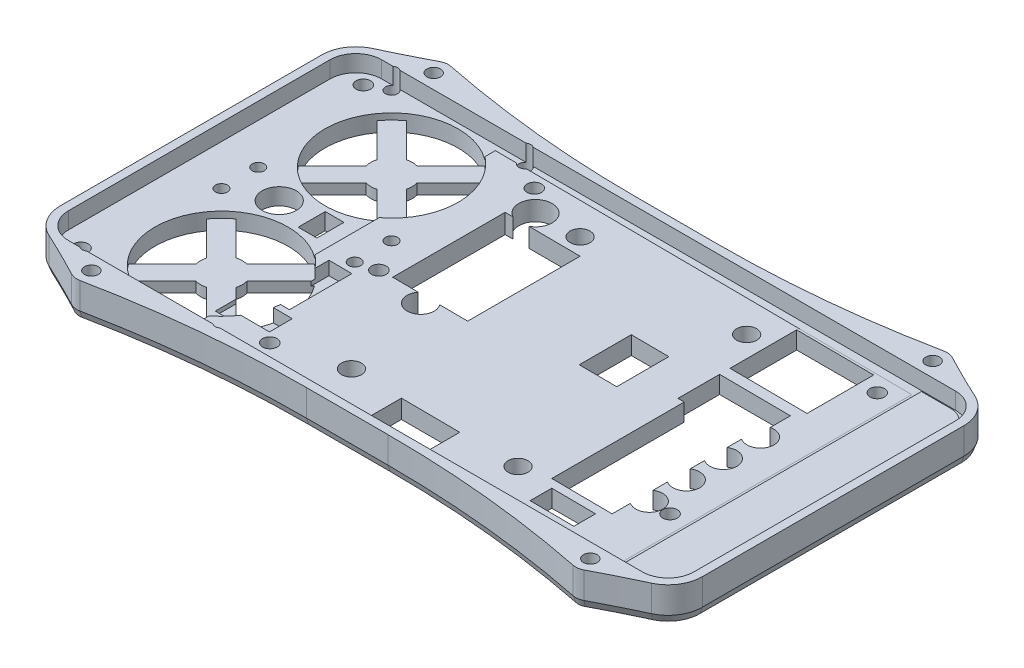
SolidWorks part; units mm, degrees
ref_plane "前视基准面" through (0, 0, 0) normal (0, 0, 1) x (1, 0, 0)
ref_plane "上视基准面" through (0, 0, 0) normal (0, 1, 0) x (1, 0, 0)
ref_plane "右视基准面" through (0, 0, 0) normal (1, 0, 0) x (0, 0, -1)
sketch "草图1" plane through (0, 0, 0) normal (0, 1, 0) x (1, 0, 0)
  line L0 (6, 0.2) -> (143.8, 0.2)
  line L1 (6, 0) -> (143.8, 0) construction
  line L2 (0, -6) -> (0, -68.8) construction
  line L3 (6, -74.8) -> (143.8, -74.8) construction
  line L4 (149.8, -6) -> (149.8, -68.8) construction
  line L5 (150, -6) -> (150, -68.8)
  line L6 (6, -75) -> (143.8, -75)
  line L7 (-0.2, -6) -> (-0.2, -68.8)
  arc A0 (143.8, 0) -> (149.8, -6) centre (143.8, -6) cw construction
  arc A1 (143.8, -74.8) -> (149.8, -68.8) centre (143.8, -68.8) ccw construction
  arc A2 (0, -68.8) -> (6, -74.8) centre (6, -68.8) ccw construction
  arc A3 (6, 0) -> (0, -6) centre (6, -6) ccw construction
  arc A4 (143.8, 0.2) -> (150, -6) centre (143.8, -6) cw
  arc A5 (143.8, -75) -> (150, -68.8) centre (143.8, -68.8) ccw
  arc A6 (-0.2, -68.8) -> (6, -75) centre (6, -68.8) ccw
  arc A7 (6, 0.2) -> (-0.2, -6) centre (6, -6) ccw
  point P7 (149.8, 0)
  point P12 (0, -74.8)
  point P15 (0, 0)
  dimension "D3" = 6
  dimension "D1" = 74.8
  dimension "D2" = 149.8
  dimension "D4" = 0.2
extrude "凸台-拉伸1" add sketch "草图1" along normal blind 4
sketch "草图2" plane through (0, 0, 0) normal (0, -1, 0) x (-1, 0, 0)
  line L0 (-122.6, -55.35) -> (-108.9, -55.35)
  line L1 (-122.6, -69.85) -> (-108.9, -69.85)
  line L2 (-122.6, -69.85) -> (-122.6, -63.95)
  line L3 (-122.6, -63.95) -> (-108.9, -63.95)
  line L4 (-108.9, -69.85) -> (-108.9, -63.95)
  line L5 (-135.3, -1.25) -> (-35.3, -1.25) construction
  line L6 (-135.3, -1.25) -> (-135.3, -73.55) construction
  line L7 (-135.3, -73.55) -> (-35.3, -73.55) construction
  line L8 (-35.3, -1.25) -> (-35.3, -73.55) construction
  line L9 (-108.9, -61.25) -> (-108.9, -55.35)
  line L10 (-122.6, -61.25) -> (-108.9, -61.25)
  line L11 (-122.6, -61.25) -> (-122.6, -55.35)
  line L12 (-122.6, -46.75) -> (-108.9, -46.75)
  line L13 (-108.9, -52.65) -> (-108.9, -46.75)
  line L14 (-122.6, -52.65) -> (-108.9, -52.65)
  line L15 (-122.6, -52.65) -> (-122.6, -46.75)
  line L16 (-122.6, -38.15) -> (-108.9, -38.15)
  line L17 (-108.9, -44.05) -> (-108.9, -38.15)
  line L18 (-122.6, -44.05) -> (-108.9, -44.05)
  line L19 (-122.6, -44.05) -> (-122.6, -38.15)
  line L20 (0, -6) -> (0, -68.8) construction
  line L21 (-35.3, -73.55) -> (-0.8, -73.55) construction
  line L22 (-120.25, -26.65) -> (-111.25, -26.65) construction
  line L23 (-120.25, -26.65) -> (-120.25, -33.15) construction
  line L24 (-120.25, -33.15) -> (-111.25, -33.15) construction
  line L25 (-111.25, -26.65) -> (-111.25, -33.15) construction
  line L26 (-85.8, -48.75) -> (-81.1, -48.75) construction
  line L27 (-85.8, -48.75) -> (-85.8, -58.15) construction
  line L28 (-85.8, -58.15) -> (-81.1, -58.15) construction
  line L29 (-81.1, -48.75) -> (-81.1, -58.15) construction
  line L30 (-71.5, -48.65) -> (-68.2, -48.65) construction
  line L31 (-71.5, -48.65) -> (-71.5, -57.55) construction
  line L32 (-71.5, -57.55) -> (-68.2, -57.55) construction
  line L33 (-68.2, -48.65) -> (-68.2, -57.55) construction
  line L34 (-43.1, -45.05) -> (-38.6, -45.05) construction
  line L35 (-43.1, -45.05) -> (-43.1, -59.05) construction
  line L36 (-43.1, -59.05) -> (-38.6, -59.05) construction
  line L37 (-38.6, -45.05) -> (-38.6, -59.05) construction
  line L38 (-45.3, -61.55) -> (-33.3, -61.55) construction
  line L39 (-45.3, -61.55) -> (-45.3, -66.05) construction
  line L40 (-45.3, -66.05) -> (-33.3, -66.05) construction
  line L41 (-33.3, -61.55) -> (-33.3, -66.05) construction
  line L42 (-0.8, -73.55) -> (-0.8, -1.25) construction
  line L43 (-0.8, -1.25) -> (-35.3, -1.25) construction
  line L44 (-149.8, -6) -> (-149.8, -68.8) construction
  line L45 (-30.8, -34.65) -> (-27.3, -34.65) construction
  line L46 (-30.8, -34.65) -> (-30.8, -40.15) construction
  line L47 (-30.8, -40.15) -> (-27.3, -40.15) construction
  line L48 (-27.3, -34.65) -> (-27.3, -40.15) construction
  line L49 (-120.75, -33.65) -> (-110.75, -33.65)
  line L50 (-110.75, -26.15) -> (-110.75, -33.65)
  line L51 (-120.75, -26.15) -> (-110.75, -26.15)
  line L52 (-120.75, -26.15) -> (-120.75, -33.65)
  line L53 (-86.3, -48.25) -> (-86.3, -58.65)
  line L54 (-86.3, -58.65) -> (-80.6, -58.65)
  line L55 (-80.6, -48.25) -> (-80.6, -58.65)
  line L56 (-86.3, -48.25) -> (-80.6, -48.25)
  line L57 (-72, -48.15) -> (-72, -58.05)
  line L58 (-72, -58.05) -> (-67.7, -58.05)
  line L59 (-67.7, -48.15) -> (-67.7, -58.05)
  line L60 (-72, -48.15) -> (-67.7, -48.15)
  line L61 (-31.3, -34.15) -> (-31.3, -40.65)
  line L62 (-31.3, -40.65) -> (-26.8, -40.65)
  line L63 (-26.8, -34.15) -> (-26.8, -40.65)
  line L64 (-31.3, -34.15) -> (-26.8, -34.15)
  line L65 (-43.6, -44.55) -> (-43.6, -59.55)
  line L66 (-43.6, -59.55) -> (-38.1, -59.55)
  line L67 (-38.1, -44.55) -> (-38.1, -59.55)
  line L68 (-43.6, -44.55) -> (-38.1, -44.55)
  line L69 (-45.8, -61.05) -> (-45.8, -66.55)
  line L70 (-45.8, -66.55) -> (-32.8, -66.55)
  line L71 (-32.8, -61.05) -> (-32.8, -66.55)
  line L72 (-45.8, -61.05) -> (-32.8, -61.05)
  circle A0 centre (-103.2, -9.35) radius 2 construction
  circle A1 centre (-103.2, -64.25) radius 2 construction
  circle A2 centre (-63.2, -64.25) radius 2 construction
  circle A3 centre (-63.2, -9.35) radius 2 construction
  circle A4 centre (-130.8, -5.6) radius 1.25 construction
  circle A5 centre (-131.1, -55.65) radius 1.25 construction
  circle A6 centre (-47.7, -4.85) radius 1.25 construction
  circle A7 centre (-48.1, -68.75) radius 1.25 construction
  circle A8 centre (-22.8, -70.3) radius 1.25 construction
  circle A9 centre (-5.05, -71.05) radius 1.25 construction
  circle A10 centre (-5.05, -3.25) radius 1.25 construction
  circle A11 centre (-19, -37.4) radius 3.6 construction
  circle A12 centre (-103.2, -9.35) radius 2.4
  circle A13 centre (-63.2, -9.35) radius 2.4
  circle A14 centre (-63.2, -64.25) radius 2.4
  circle A15 centre (-103.2, -64.25) radius 2.4
  circle A16 centre (-19, -37.4) radius 4.1
  circle A17 centre (-130.8, -5.6) radius 1.75
  circle A18 centre (-131.1, -55.65) radius 1.75
  circle A19 centre (-48.1, -68.75) radius 1.75
  circle A20 centre (-22.8, -70.3) radius 1.75
  circle A21 centre (-5.05, -71.05) radius 1.75
  circle A22 centre (-5.05, -3.25) radius 1.75
  circle A23 centre (-47.7, -4.85) radius 1.75
  circle A24 centre (-46.11, -40.57) radius 1.25 construction
  circle A25 centre (-46.11, -40.57) radius 1.75
  point P22 (0, -37.4)
  point P23 (-135.3, -37.4)
  point P28 (-115.75, -33.15)
  point P29 (-115.75, -38.15)
  point P30 (-111.25, -29.9)
  point P31 (-108.9, -41.1)
  point P79 (-0.8, -37.4)
  point P81 (-27.3, -37.4)
  dimension "D21" = 4
  dimension "D34" = 2.5
  dimension "D53" = 7.2
  dimension "D1" = 13.7
  dimension "D2" = 5.9
  dimension "D3" = 72.3
  dimension "D4" = 3.7
  dimension "D5" = 12.7
  dimension "D7" = 14.5
  dimension "D8" = 100
  dimension "D9" = 2.7
  dimension "D10" = 9
  dimension "D11" = 6.5
  dimension "D12" = 11.2
  dimension "D13" = 15.4
  dimension "D14" = 9.4
  dimension "D15" = 4.7
  dimension "D16" = 23.1
  dimension "D17" = 3.3
  dimension "D18" = 8.9
  dimension "D19" = 16
  dimension "D20" = 37.4
  dimension "D22" = 8.1
  dimension "D23" = 32.1
  dimension "D24" = 40
  dimension "D25" = 9.3
  dimension "D26" = 14
  dimension "D27" = 4.5
  dimension "D28" = 12
  dimension "D29" = 4.5
  dimension "D30" = 3.3
  dimension "D31" = 2
  dimension "D32" = 7.5
  dimension "D33" = 14.5
  dimension "D35" = 34.5
  dimension "D36" = 2
  dimension "D37" = 4.25
  dimension "D38" = 2.5
  dimension "D39" = 3.25
  dimension "D40" = 22
  dimension "D41" = 4.8
  dimension "D42" = 12.8
  dimension "D43" = 3.6
  dimension "D44" = 12.4
  dimension "D45" = 4.35
  dimension "D46" = 4.5
  dimension "D47" = 4.2
  dimension "D48" = 17.9
  dimension "D49" = 18.2
  dimension "D50" = 3.5
  dimension "D51" = 5.5
  dimension "D52" = 8.3
  dimension "D58" = 28.18
  dimension "D59" = 1.99
  dimension "D54" = 0.4
  dimension "D55" = 0.5
  dimension "D56" = 0.5
  dimension "D57" = 0.5
  dimension "D6" = 4
sketch "草图7" plane through (0, 0, -0.2) normal (0, 0, -1) x (-1, 0, 0)
  line L0 (-135.3, 4) -> (-35.3, 4.75)
  line L2 (-35.3, 4.75) -> (-35.3, 4)
  line L4 (-35.3, 4) -> (-135.3, 4)
  line L6 (-143.8, 4) -> (-6, 4) construction
  dimension "D1" = 0.75
extrude "凸台-拉伸11" add sketch "草图7" against normal offset from surface (71.2 mm away) 2 from offset 2 up to face at (74.9, 2, 75) offset against normal yes
extrude "切除-拉伸1" cut sketch "草图2" against normal blind 10 contours A12 | A13 | A14 | A15
sketch "草图3" plane through (0, 0, 0) normal (0, 1, 0) x (1, 0, 0)
  line L0 (136.8, -1) -> (136.8, -73.8)
  line L1 (143.8, 0) -> (135.8, 0) construction
  line L2 (149.8, -6) -> (149.8, -68.8) construction
  line L3 (143.8, -74.8) -> (135.8, -74.8) construction
  line L4 (135.8, 0) -> (135.8, -74.8) construction
  line L5 (6, -74.8) -> (143.8, -74.8) construction
  line L6 (135.3, -1.25) -> (135.3, -73.55) construction
  line L7 (143.8, -73.8) -> (136.8, -73.8)
  line L8 (148.8, -6) -> (148.8, -68.8)
  line L9 (143.8, -1) -> (136.8, -1)
  arc A0 (143.8, 0) -> (149.8, -6) centre (143.8, -6) cw construction
  arc A1 (149.8, -68.8) -> (143.8, -74.8) centre (143.8, -68.8) cw construction
  arc A2 (148.8, -68.8) -> (143.8, -73.8) centre (143.8, -68.8) cw
  arc A3 (143.8, -1) -> (148.8, -6) centre (143.8, -6) cw
  point P17 (149.8, 0)
  dimension "D1" = 6
  dimension "D2" = 0.5
extrude "凸台-拉伸9" add sketch "草图3" along normal offset from surface (5 mm away) 1 up to face at (85.3, 4, 37.4) offset beyond the face yes
sketch "草图4" plane through (0, 0, 0) normal (0, 1, 0) x (1, 0, 0)
  line L0 (125.2, -20.85) -> (108.2, -20.85)
  line L1 (108.2, -30.85) -> (109.7, -30.85)
  line L2 (109.7, -30.85) -> (109.7, -62.65)
  line L3 (111.7, -69.85) -> (111.7, -62.65)
  line L4 (49.2, -40.35) -> (49.2, -13.35)
  line L5 (108.2, -30.85) -> (108.2, -20.85)
  line L6 (111.7, -69.85) -> (122.2, -69.85)
  line L7 (108.2, -30.85) -> (125.2, -30.85) construction
  line L8 (109.7, -62.65) -> (124.2, -62.65)
  line L9 (80.466, -18.85) -> (96.6871, -18.85) construction
  line L10 (107.2, 11.628) -> (107.2, 24.7853) construction
  line L11 (49.2, -13.35) -> (67.2, -13.35)
  line L12 (125.2, -30.85) -> (124.2, -30.85)
  line L13 (124.2, -30.85) -> (124.2, -62.65)
  line L14 (124.2, -62.65) -> (122.2, -62.65)
  line L15 (122.2, -62.65) -> (122.2, -69.85)
  line L16 (67.2, -13.35) -> (67.2, -40.35)
  line L17 (67.2, -40.35) -> (49.2, -40.35)
  line L18 (63.2, -9.35) -> (46.0308, -9.35) construction
  line L20 (111.7, -64.65) -> (122.2, -64.65)
  line L21 (125.2, -20.85) -> (125.2, -30.85)
  line L33 (89.5, -35.85) -> (89.5, -23.35)
  line L34 (89.5, -23.35) -> (98.5, -23.35)
  line L35 (98.5, -23.35) -> (98.5, -35.85)
  line L36 (98.5, -35.85) -> (89.5, -35.85)
  line L39 (108.2, -18.35) -> (108.2, -2.35)
  line L40 (108.2, -2.35) -> (126.7, -2.35)
  line L41 (126.7, -2.35) -> (126.7, -18.35)
  line L42 (126.7, -18.35) -> (108.2, -18.35)
  line L43 (89.2, -64.25) -> (89.2, -73.25)
  line L44 (89.2, -73.25) -> (75.2, -73.25)
  line L45 (75.2, -73.25) -> (75.2, -64.25)
  line L46 (75.2, -64.25) -> (89.2, -64.25)
  circle A0 centre (103.2, -9.35) radius 2.4 construction
  circle A1 centre (103.2, -64.25) radius 2.4 construction
  circle A2 centre (103.2, -64.25) radius 2.4
  circle A3 centre (63.2, -64.25) radius 2.4 construction
  circle A4 centre (63.2, -64.25) radius 2.4
  circle A5 centre (103.2, -9.35) radius 2.4 construction
  circle A6 centre (126, -28.85) radius 3.25
  circle A7 centre (126, -37.75) radius 3.25
  circle A8 centre (126, -46.65) radius 3.25
  circle A9 centre (126, -55.55) radius 3.25
  circle A10 centre (63.2, -9.35) radius 2.4 construction
  circle A11 centre (63.2, -9.35) radius 2.4 construction
  circle A12 centre (57.9, -42.35) radius 3.25
  circle A13 centre (53, -9.85) radius 4
  point P7 (122.2, -66.25)
  point P30 (67.2, -26.85)
  dimension "D7" = 9.5
  dimension "D30" = 5
  dimension "D40" = 6.5
  dimension "D18" = 6.5
  dimension "D21" = 8
  dimension "D4" = 11.5
  dimension "D5" = 49
  dimension "D6" = 10
  dimension "D8" = 4
  dimension "D9" = 5.2
  dimension "D10" = 5
  dimension "D11" = 17
  dimension "D12" = 6.5
  dimension "D13" = 1
  dimension "D14" = 14
  dimension "D15" = 18
  dimension "D16" = 4
  dimension "D17" = 27
  dimension "D19" = 33
  dimension "D20" = 5.3
  dimension "D22" = 10.2
  dimension "D23" = 0.5
  dimension "D24" = 2
  dimension "D25" = 12.5
  dimension "D26" = 2
  dimension "D27" = 9
  dimension "D31" = 18.5
  dimension "D32" = 9
  dimension "D33" = 16
  dimension "D34" = 14
  dimension "D35" = 14
  dimension "D36" = 9
  dimension "D37" = 9
  dimension "D38" = 2
  dimension "D39" = 19.5
  dimension "D41" = 22.8
  dimension "D43" = 14
  dimension "D44" = 4.7
  dimension "D42" = 4
extrude "拉伸-薄壁1" add sketch "草图1<2>" along normal blind 8 thin thin type one direction wall 2
sketch "草图1<2>" plane through (0, 0, 0) normal (0, 1, 0) x (1, 0, 0) same geometry as "草图1"
extrude "切除-拉伸2" cut sketch "草图4" along normal through all contours L20 L3 L6 L15 | L41 L42 L39 L40 | L8 L2 L1 L5 L0 L21 L12 L13 | A6 | A7 | A8 | A9 | L46 L43 L44 L45 | L35 L36 L33 L34 | L4 L11 L16 L17 | A13 | A12 region at (116.95, 0, 67.25)
extrude "切除-拉伸3" cut sketch "草图2<11>" against normal through all contours L61 L62 L63 L64 | A16
sketch "草图2<11>" plane through (0, 0, 0) normal (0, -1, 0) x (-1, 0, 0) same geometry as "草图2"
extrude "切除-拉伸4" cut sketch "草图2<13>" against normal through all contours A17 | A18 | A19 | A23 | A22 | A21 | A25
sketch "草图2<13>" plane through (0, 0, 0) normal (0, -1, 0) x (-1, 0, 0) same geometry as "草图2"
extrude "切除-拉伸5" cut sketch "草图2<14>" against normal through all from offset 1.5 contours L67 L66 L65 L68 | L71 L70 L69 L72 offset against normal yes
sketch "草图2<14>" plane through (0, 0, 0) normal (0, -1, 0) x (-1, 0, 0) same geometry as "草图2"
sketch "草图5" plane through (0, 0, 0) normal (0, -1, 0) x (-1, 0, 0)
  text T0 "<b>M3*6</b>" font "@Adobe 黑体 Std R" height 7
  text T1 "<b>M3*6</b>" font "@Adobe 黑体 Std R" height 7
  text T2 "<b>M3*6</b>" font "@Adobe 黑体 Std R" height 7
  text T3 "<b>M3*6</b>" font "@Adobe 黑体 Std R" height 7
extrude "切除-拉伸6" [suppressed] cut sketch "草图5" against normal blind 0.6
sketch "草图6" plane through (0, 0, 0) normal (0, 1, 0) x (1, 0, 0)
  line L1 (0, -6) -> (0, -68.8) construction
  line L2 (149.8, -6) -> (149.8, -68.8) construction
  line L4 (6, 0.2) -> (143.8, 0.2) construction
  line L5 (6, -75) -> (143.8, -75) construction
  circle A0 centre (15, 3.7) radius 1.5 construction
  circle A1 centre (15, -78.5) radius 1.5 construction
  circle A2 centre (134.8, 3.7) radius 1.5 construction
  circle A3 centre (134.8, -78.5) radius 1.5 construction
  circle A4 centre (15, 3.7) radius 3.5
  circle A5 centre (15, -78.5) radius 3.5
  circle A6 centre (134.8, 3.7) radius 3.5
  circle A7 centre (134.8, -78.5) radius 3.5
  circle A8 centre (15, 3.7) radius 1.65
  circle A9 centre (134.8, 3.7) radius 1.65
  circle A10 centre (134.8, -78.5) radius 1.65
  circle A11 centre (15, -78.5) radius 1.65
  dimension "D1" = 3
  dimension "D3" = 0.15
  dimension "D4" = 15
  dimension "D5" = 15
  dimension "D2" = 2
extrude "凸台-拉伸10" add sketch "草图6" along normal up to surface (8 mm away) up to face at (74.9, 8, 37.4)
extrude "切除-拉伸9" cut sketch "草图6<2>" along normal through all contours A8 | A9 | A10 | A11
sketch "草图6<2>" plane through (0, 0, 0) normal (0, 1, 0) x (1, 0, 0) same geometry as "草图6"
fillet "圆角1" radius 250 8 edges at (18.1623, 4, 77) (11.8377, 4, 77) (131.6377, 4, 77) (137.9623, 4, 77) (137.9623, 4, -2.2) (131.6377, 4, -2.2) (11.8377, 4, -2.2) (18.1623, 4, -2.2)
chamfer "倒角1" distance 0.6 angle 70 20 edges at (40.2731, 0, 78.2358) (14.5029, 0, 81.9645) (74.9, 0, 77) (7.988, 0, 78.8506) (109.5269, 0, 78.2358) (-0.9143, 0, 73.2083) (135.2971, 0, 81.9645) (-2.2, 0, 37.4) (141.812, 0, 78.8506) (-0.9143, 0, 1.5917) (150.7143, 0, 73.2083) (7.988, 0, -4.0506) (152, 0, 37.4) (14.5029, 0, -7.1645) (150.7143, 0, 1.5917) (40.2731, 0, -3.4358) (141.812, 0, -4.0506) (74.9, 0, -2.2) (135.2971, 0, -7.1645) (109.5269, 0, -3.4358) first distance on face at (134.8, 0, 80.15)
sketch "草图8" plane through (0, 0, 0) normal (0, -1, 0) x (1, 0, 0)
  line L0 (9.5525, 32.9807) -> (9.5525, 0.9807) construction
  line L1 (9.5525, 0.9807) -> (41.5525, 0.9807) construction
  line L2 (41.5525, 0.9807) -> (41.5525, 32.9807) construction
  line L3 (41.5525, 32.9807) -> (9.5525, 32.9807) construction
  line L4 (31.3, 37.4) -> (26.8, 37.4) construction
  line L7 (41.5525, 41.8193) -> (9.5525, 41.8193) construction
  line L8 (41.5525, 73.8193) -> (41.5525, 41.8193) construction
  line L9 (9.5525, 73.8193) -> (41.5525, 73.8193) construction
  line L10 (9.5525, 41.8193) -> (9.5525, 73.8193) construction
  circle A0 centre (41.5525, 0.9807) radius 1.45
  circle A1 centre (41.5525, 32.9807) radius 1.45
  circle A2 centre (9.5525, 32.9807) radius 1.45
  circle A3 centre (9.5525, 0.9807) radius 1.45
  circle A4 centre (9.5525, 73.8193) radius 1.45
  circle A5 centre (9.5525, 41.8193) radius 1.45
  circle A6 centre (41.5525, 41.8193) radius 1.45
  circle A7 centre (41.5525, 73.8193) radius 1.45
  point P4 (9.5525, 16.9807)
  dimension "D3" = 2.9
  dimension "D4" = 2.9
  dimension "D5" = 2.9
  dimension "D6" = 2.9
  dimension "D1" = 32
  dimension "D2" = 32
extrude "切除-拉伸10" cut sketch "草图8" against normal through all
sketch "草图9" plane through (0, 0, 0) normal (0, -1, 0) x (1, 0, 0)
  line L0 (9.5525, 32.9807) -> (41.5525, 32.9807) construction
  line L1 (41.5525, 32.9807) -> (41.5525, 0.9807) construction
  line L2 (41.5525, 0.9807) -> (9.5525, 0.9807) construction
  line L3 (9.5525, 0.9807) -> (9.5525, 32.9807) construction
  line L4 (9.5525, 32.9807) -> (41.5525, 0.9807) construction
  line L5 (41.5525, 32.9807) -> (9.5525, 0.9807) construction
  line L6 (13.088, 32.9807) -> (41.5525, 4.5163)
  line L7 (41.5525, 4.5163) -> (38.017, 0.9807)
  line L8 (38.017, 0.9807) -> (9.5525, 29.4452)
  line L9 (9.5525, 29.4452) -> (13.088, 32.9807)
  line L10 (38.017, 32.9807) -> (9.5525, 4.5163)
  line L11 (9.5525, 4.5163) -> (13.088, 0.9807)
  line L12 (13.088, 0.9807) -> (41.5525, 29.4452)
  line L13 (41.5525, 29.4452) -> (38.017, 32.9807)
  line L14 (9.5525, 0.9807) -> (41.5525, 0.9807) construction
  line L15 (31.3, 37.4) -> (26.8, 37.4) construction
  line L18 (9.5525, 73.8193) -> (41.5525, 73.8193) construction
  line L19 (9.5525, 41.8193) -> (41.5525, 73.8193) construction
  line L20 (9.5525, 73.8193) -> (9.5525, 41.8193) construction
  line L21 (41.5525, 73.8193) -> (9.5525, 73.8193) construction
  line L22 (41.5525, 41.8193) -> (41.5525, 73.8193) construction
  line L23 (9.5525, 41.8193) -> (41.5525, 41.8193) construction
  line L24 (41.5525, 45.3548) -> (38.017, 41.8193)
  line L25 (13.088, 73.8193) -> (41.5525, 45.3548)
  line L26 (9.5525, 70.2837) -> (13.088, 73.8193)
  line L27 (38.017, 41.8193) -> (9.5525, 70.2837)
  line L28 (9.5525, 45.3548) -> (13.088, 41.8193)
  line L29 (38.017, 73.8193) -> (9.5525, 45.3548)
  line L30 (41.5525, 70.2837) -> (38.017, 73.8193)
  line L31 (13.088, 41.8193) -> (41.5525, 70.2837)
  line L32 (41.5525, 41.8193) -> (9.5525, 73.8193) construction
  circle A0 centre (25.5525, 16.9807) radius 16
  circle A1 centre (25.5525, 16.9807) radius 5
  circle A2 centre (25.5525, 57.8193) radius 5
  circle A3 centre (25.5525, 57.8193) radius 16
  dimension "D2" = 10
  dimension "D4" = 5
extrude "切除-拉伸11" cut sketch "草图9" against normal blind 10 contours A1 L10 A0 L6 | A1 L6 A0 L12 | A1 L12 A0 L8 | A1 L8 A0 L10 | A3 L29 A2 L27 | A3 L25 A2 L29 | A3 L31 A2 L25 | A3 L27 A2 L31 region at (25.5525, 0, 28.2322) region at (14.301, 0, 16.9807) region at (36.804, 0, 16.9807) region at (25.5525, 0, 5.7292) region at (36.804, 0, 57.8193) region at (25.5525, 0, 46.5678) region at (14.301, 0, 57.8193) region at (25.5525, 0, 69.0708)
sketch "草图10" plane through (0, 4, 0) normal (0, 1, 0) x (1, 0, 0)
  circle A0 centre (25.5525, -16.9807) radius 16
  circle A1 centre (25.5525, -57.8193) radius 16
  dimension "D1" = 32
  dimension "D2" = 32
extrude "切除-拉伸12" cut sketch "草图10" against normal mid plane 3
equation "\"D1@草图3\"=\"D3@草图1\""
